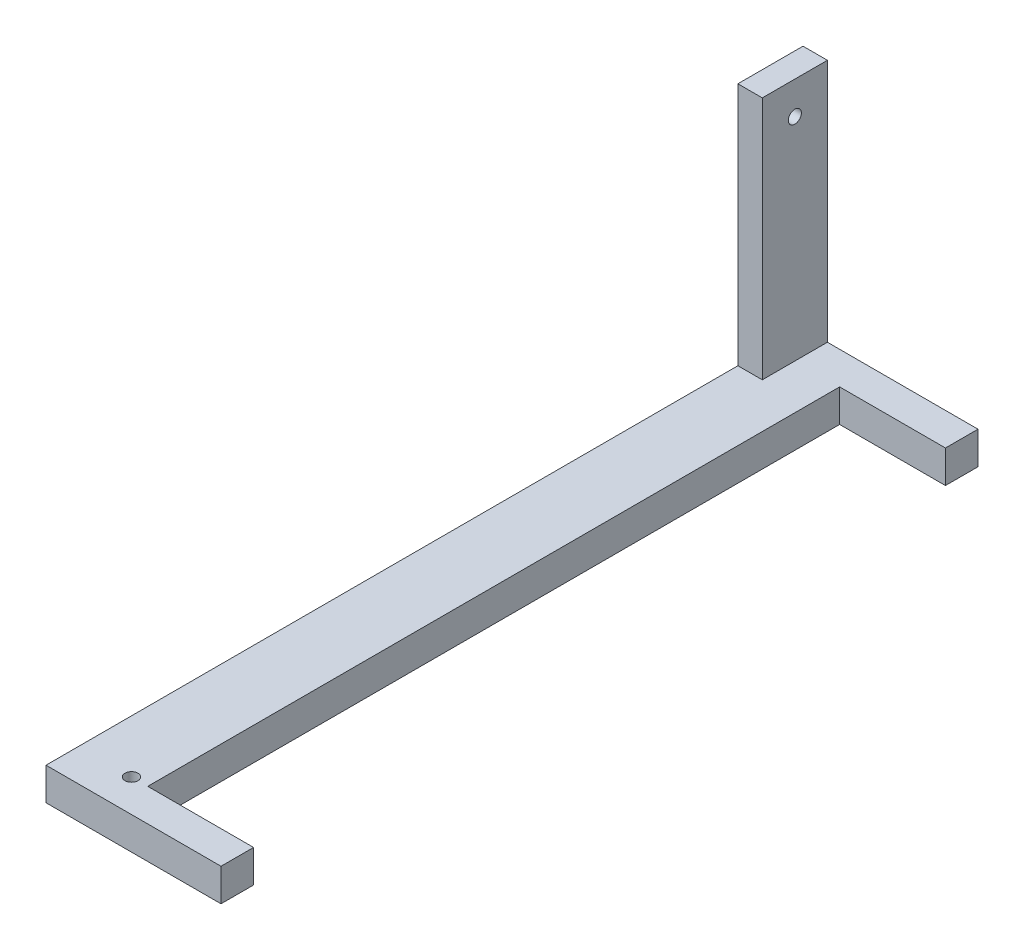
SolidWorks part; units mm, degrees
ref_plane "Front Plane" through (0, 0, 0) normal (0, 0, 1) x (1, 0, 0)
ref_plane "Top Plane" through (0, 0, 0) normal (0, 1, 0) x (1, 0, 0)
ref_plane "Right Plane" through (0, 0, 0) normal (1, 0, 0) x (0, 0, -1)
sketch "Sketch1" plane through (0, 0, 0) normal (1, 0, 0) x (0, 0, -1)
  line L0 (0, 0) -> (-8, 0)
  line L1 (-8, 0) -> (-8, -8)
  line L2 (-8, -8) -> (178, -8)
  line L3 (178, -8) -> (178, 0)
  line L4 (178, 0) -> (170, 0)
  line L5 (170, 0) -> (0, 0)
  point P8 (0, 0)
  dimension "D1" = 170
  dimension "D2" = 8
extrude "Boss-Extrude1" add sketch "Sketch1" along normal blind 4
sketch "Sketch2" plane through (4, 0, 0) normal (1, 0, 0) x (0, 0, -1)
  line L0 (178, 0) -> (-8, 0) construction
  line L1 (-8, -8) -> (0, -8)
  line L2 (-8, -8) -> (-8, 0)
  line L3 (-8, 0) -> (0, 0)
  line L4 (0, -8) -> (0, 0)
  line L5 (-8, -8) -> (178, -8) construction
  line L6 (178, 0) -> (170, 0)
  line L7 (178, 0) -> (178, -8)
  line L8 (178, -8) -> (170, -8)
  line L9 (170, 0) -> (170, -8)
extrude "Boss-Extrude2" add sketch "Sketch2" along normal blind 26
extrude "Boss-Extrude3" add sketch "Sketch1<2>" against normal blind 7
sketch "Sketch1<2>" plane through (0, 0, 0) normal (1, 0, 0) x (0, 0, -1) same geometry as "Sketch1"
sketch "Sketch4" plane through (-7, 0, 0) normal (-1, 0, 0) x (0, 0, 1)
  line L0 (-178, 0) -> (-178, 60)
  line L1 (-178, 60) -> (-162, 60)
  line L2 (-162, 60) -> (-162, 0)
  line L3 (-170, 0) -> (0, 0) construction
  line L4 (-170, 60) -> (-170, 52) construction
  line L5 (-170, 52) -> (-170, 0) construction
  line L6 (-178, -8) -> (-178, 0) construction
  line L8 (8, -8) -> (-178, -8)
  line L9 (8, -8) -> (8, 0)
  line L10 (8, 0) -> (-162, 0)
  line L11 (-178, -8) -> (-178, 0)
  point P7 (-170, 60)
  point P8 (-170, 52)
  dimension "D1" = 52
extrude "Boss-Extrude4" add sketch "Sketch4" along normal blind 6
hole_wizard "M3 Clearance Hole1" positions "3DSketch2" profile "Sketch5" hole size "M3" standard "ANSI Metric" end condition through all
sketch3d "3DSketch2"
  point P0 (0, 0, 0)
  point P3 (0, 0, 0)
  point P5 (0, 0, 0)
  point P7 (0, 0, 0)
  point P9 (0, 0, 0)
sketch "Sketch5" plane through (0, 0, 0) normal (1, 0, 0) x (0, 0, 1)
  line L0 (0, 0) -> (0, 8)
  line L1 (0, 8) -> (1.6, 8)
  line L2 (1.6, 8) -> (1.6, 0)
  line L5 (1.6, 0) -> (0, 0)
  line L11 (0, -6.35) -> (0, 107.95) construction
  dimension "Thru Hole Dia." = 3.2
  dimension "Thru Hole Depth" = 8
hole_wizard "M3 Clearance Hole2" positions "3DSketch3" profile "Sketch6" hole size "M3" standard "ANSI Metric" end condition through all
sketch3d "3DSketch3"
  point P0 (-7, 52, -170)
sketch "Sketch6" plane through (-7, 52, -170) normal (0, 1, 0) x (0, 0, -1)
  line L0 (0, 0) -> (0, 6)
  line L1 (0, 6) -> (1.6, 6)
  line L2 (1.6, 6) -> (1.6, 0)
  line L5 (1.6, 0) -> (0, 0)
  line L11 (0, -6.35) -> (0, 107.95) construction
  dimension "Thru Hole Dia." = 3.2
  dimension "Thru Hole Depth" = 6
